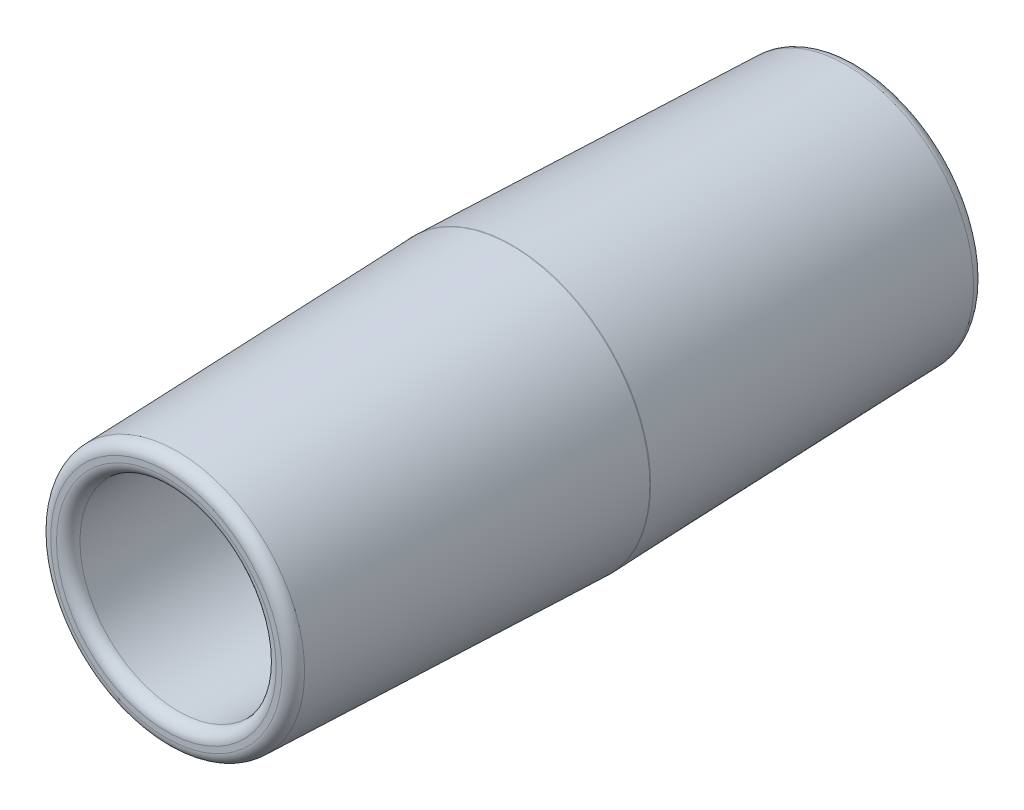
SolidWorks part; units mm, degrees
ref_plane "Front Plane" through (0, 0, 0) normal (0, 0, 1) x (1, 0, 0)
ref_plane "Top Plane" through (0, 0, 0) normal (0, 1, 0) x (1, 0, 0)
ref_plane "Right Plane" through (0, 0, 0) normal (1, 0, 0) x (0, 0, -1)
sketch "Sketch1" plane through (0, 0, 0) normal (0, 1, 0) x (1, 0, 0)
  line L0 (0, 39.2734) -> (0, -49.9297) construction
  line L1 (8.5, 30) -> (9.5, 0)
  line L2 (9.5, 0) -> (8.5, -30)
  line L3 (8.5, -30) -> (11, -30)
  line L4 (11, -30) -> (12, 0)
  line L5 (12, 0) -> (11, 30)
  line L6 (11, 30) -> (8.5, 30)
  line L7 (0, 0) -> (64.1719, 0) construction
  point P11 (0, 0)
  point P12 (0, 0)
  point P13 (0, 0)
  point P14 (27.0151, -40.7685)
  dimension "D1" = 8.5
  dimension "D2" = 8.5
  dimension "D3" = 9.5
  dimension "D4" = 11
  dimension "D5" = 30
revolve "Revolve1" add sketch "Sketch1" angle 360 about L0
fillet "Fillet3" radius 1 5 edges at (-12, 0, 0) (-8.5, 0, -30) (-11, 0, -30) (-8.5, 0, 30) (-11, 0, 30)
fillet "Fillet4" radius 1 1 edges at (-9.5, 0, 0)
